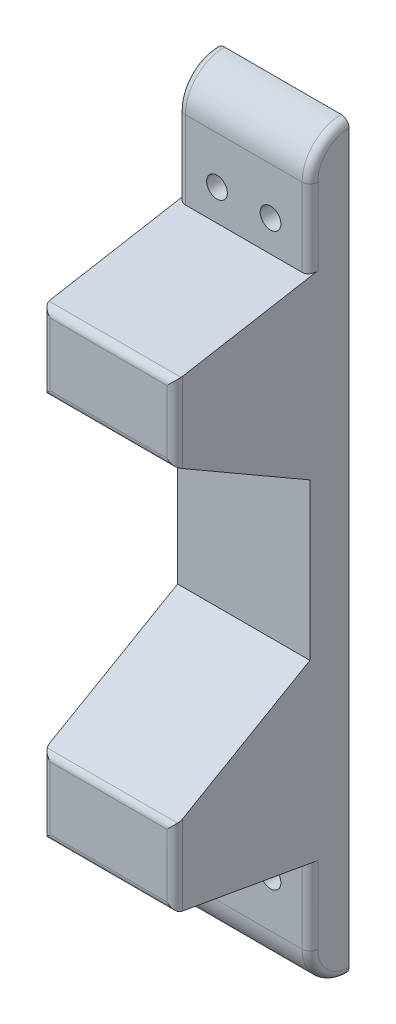
SolidWorks part; units mm, degrees
ref_plane "前视基准面" through (0, 0, 0) normal (0, 0, 1) x (1, 0, 0)
ref_plane "上视基准面" through (0, 0, 0) normal (0, 1, 0) x (1, 0, 0)
ref_plane "右视基准面" through (0, 0, 0) normal (1, 0, 0) x (0, 0, -1)
other "Configuration Table"
sketch "草图1" plane through (0, 0, 0) normal (0, 0, 1) x (1, 0, 0)
  line L1 (-6.85, 73) -> (6.85, 73) construction
  line L2 (-6.85, 73) -> (-6.85, -73) construction
  line L3 (-6.85, -73) -> (6.85, -73) construction
  line L4 (6.85, 73) -> (6.85, -73) construction
  line L5 (0, -73) -> (0, 73) construction
  line L6 (-6.85, 0) -> (6.85, 0) construction
  line L7 (-16.9328, -95) -> (16.9328, -95)
  line L8 (-16.9328, -95) -> (-16.9328, 95)
  line L9 (-16.9328, 95) -> (16.9328, 95)
  line L10 (16.9328, -95) -> (16.9328, 95)
  line L11 (0, 95) -> (0, -95) construction
  line L12 (-16.9328, 0) -> (16.9328, 0) construction
  circle A0 centre (-6.85, 73) radius 2.65
  circle A1 centre (6.85, 73) radius 2.65
  circle A2 centre (-6.85, -73) radius 2.65
  circle A3 centre (6.85, -73) radius 2.65
  point P0 (0, 0)
  point P8 (0, 0)
  dimension "D3" = 5.3
  dimension "D5" = 22
  dimension "D1" = 13.7
  dimension "D2" = 146
  dimension "D4" = 33.8656
extrude "凸台-拉伸1" add sketch "草图1" along normal blind 10
fillet "圆角1" radius 10 2 edges at (0, -95, 10) (0, 95, 10)
sketch "草图2" plane through (-16.9328, 0, 0) normal (-1, 0, 0) x (0, 0, 1)
  line L0 (0, 0) -> (108.3268, 0) construction
  line L1 (10, 65) -> (44.6, 58.8991)
  line L2 (0, 95) -> (0, -95)
  line L3 (10, -85) -> (10, 85)
  line L4 (0, 95) -> (0, -95)
  line L5 (10, -85) -> (10, 85)
  line L6 (44.6, 58.8991) -> (44.6, 39.9763)
  line L7 (44.6, 39.9763) -> (10, 20)
  line L8 (10, 85) -> (10, -85) construction
  line L9 (10, -65) -> (44.6, -58.8991)
  line L10 (44.6, -58.8991) -> (44.6, -39.9763)
  line L11 (44.6, -39.9763) -> (10, -20)
  arc A2 (0, -95) -> (10, -85) centre (0, -85) ccw
  arc A3 (10, 85) -> (0, 95) centre (0, 85) ccw
  arc A4 (0, -95) -> (10, -85) centre (0, -85) ccw
  arc A5 (10, 85) -> (0, 95) centre (0, 85) ccw
  point P7 (0, 0)
  point P11 (44.6, 36.2075)
  point P14 (10, 22.9465)
  point P17 (10, 68.5288)
  point P18 (44.6, 39.3657)
  point P19 (10, 18.4171)
  point P20 (10, 68.0007)
  point P21 (44.6, 34.1804)
  point P22 (44.6, 32.4231)
  point P23 (44.6, 24.1769)
  point P24 (44.6, 58.6012)
  point P25 (10, 66.1975)
  point P26 (10, 14.2225)
  point P27 (44.6, 64.0261)
  point P28 (44.6, 63.7054)
  point P29 (10, 67.192)
  dimension "D2" = 44.6
  dimension "D3" = 60
  dimension "D4" = 80
  dimension "D5" = 20
  dimension "D6" = 45
  dimension "D1" = 0
extrude "凸台-拉伸2" add sketch "草图2" against normal through all contours L7 L6 L1 L5 | L10 L11 L5 L9 region at (-16.9328, 45.4971, 24.9475) region at (-16.9328, -45.4971, 24.9475)
fillet "圆角2" radius 2 16 edges at (-16.9328, 92.0711, 7.0711) (16.9328, 92.0711, 7.0711) (16.9328, -92.0711, 7.0711) (-16.9328, -92.0711, 7.0711) (-16.9328, 75, 10) (16.9328, 75, 10) (-16.9328, 49.4377, 44.6) (0, 39.9763, 44.6) (0, 58.8991, 44.6) (16.9328, 49.4377, 44.6) (-16.9328, -49.4377, 44.6) (16.9328, -49.4377, 44.6) (0, -39.9763, 44.6) (0, -58.8991, 44.6) (16.9328, -75, 10) (-16.9328, -75, 10)
